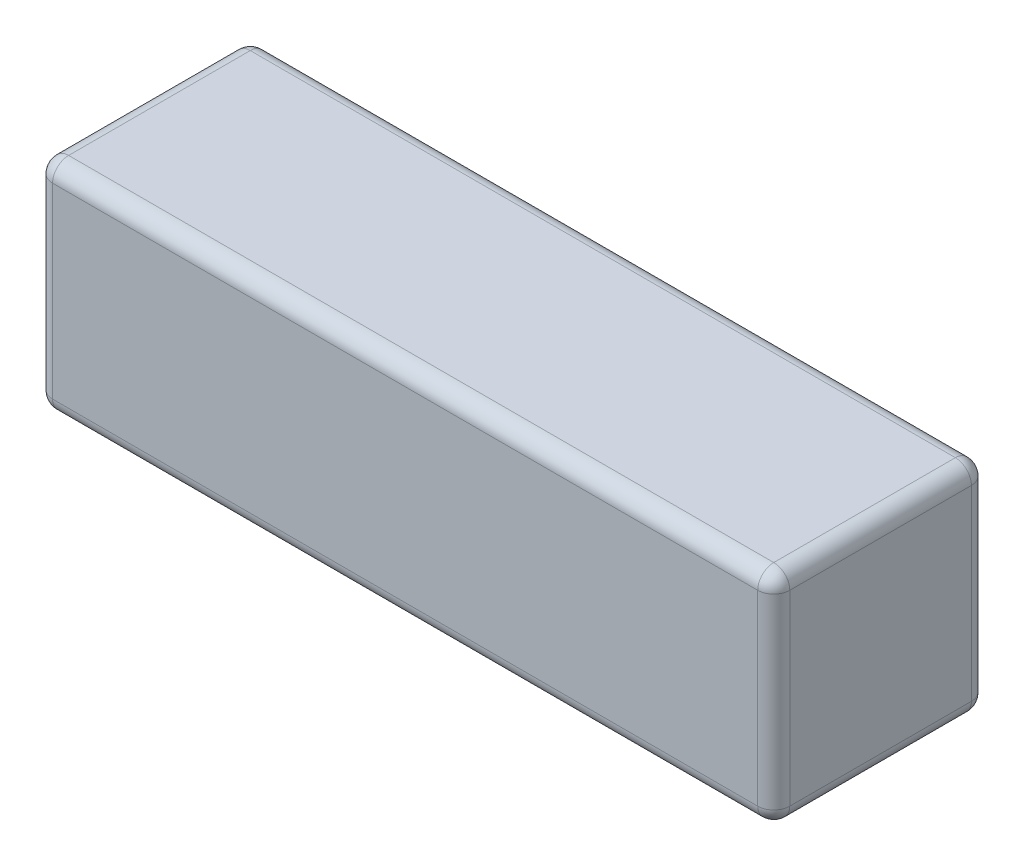
SolidWorks part; units mm, degrees
ref_plane "前视基准面" through (0, 0, 0) normal (0, 0, 1) x (1, 0, 0)
ref_plane "上视基准面" through (0, 0, 0) normal (0, 1, 0) x (1, 0, 0)
ref_plane "右视基准面" through (0, 0, 0) normal (1, 0, 0) x (0, 0, -1)
sketch "草图1" plane through (0, 0, 0) normal (0, 0, 1) x (1, 0, 0)
  line L1 (69, -20.5) -> (-69, -20.5)
  line L2 (69, -20.5) -> (69, 20.5)
  line L3 (69, 20.5) -> (-69, 20.5)
  line L4 (-69, -20.5) -> (-69, 20.5)
  line L5 (69, -20.5) -> (-69, 20.5) construction
  line L6 (69, 20.5) -> (-69, -20.5) construction
  point P0 (0, 0)
  dimension "D1" = 41
  dimension "D2" = 138
extrude "凸台-拉伸1" add sketch "草图1" along normal blind 40
fillet "圆角1" radius 3 12 edges at (-69, 20.5, 20) (0, 20.5, 0) (-69, 0, 0) (-69, -20.5, 20) (0, -20.5, 0) (69, -20.5, 20) (69, 20.5, 20) (69, 0, 0) (0, 20.5, 40) (69, 0, 40) (0, -20.5, 40) (-69, 0, 40)
